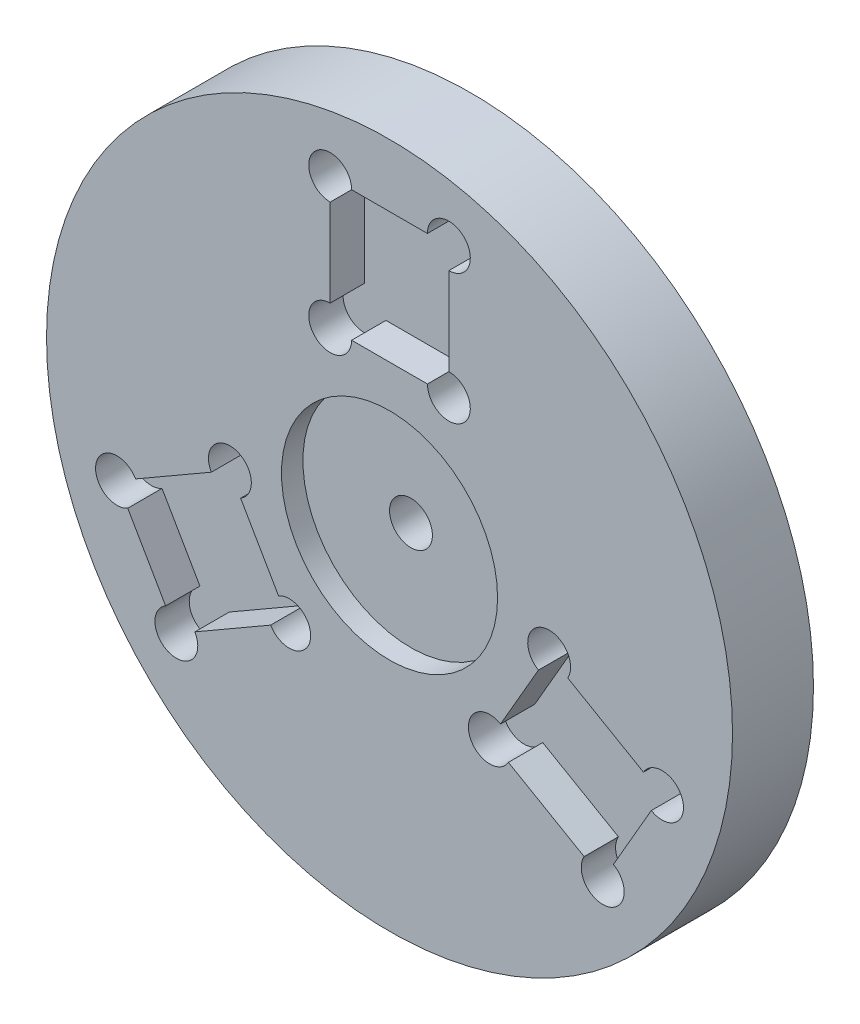
SolidWorks part; units mm, degrees
material "Beech"
ref_plane "Front Plane" through (0, 0, 0) normal (0, 0, 1) x (1, 0, 0)
ref_plane "Top Plane" through (0, 0, 0) normal (0, 1, 0) x (1, 0, 0)
ref_plane "Right Plane" through (0, 0, 0) normal (1, 0, 0) x (0, 0, -1)
sketch "Sketch1" plane through (0, 0, 0) normal (0, 0, 1) x (1, 0, 0)
  line L1 (-50.8, 50.8) -> (50.8, 50.8) construction
  line L2 (-50.8, 50.8) -> (-50.8, -50.8) construction
  line L3 (-50.8, -50.8) -> (50.8, -50.8) construction
  line L4 (50.8, 50.8) -> (50.8, -50.8) construction
  line L5 (-50.8, 50.8) -> (50.8, -50.8) construction
  line L6 (-50.8, -50.8) -> (50.8, 50.8) construction
  circle A0 centre (0, 0) radius 50.8
  point P0 (0, 0)
  dimension "D1" = 101.6
extrude "Boss-Extrude1" add sketch "Sketch1" along normal blind 11.9888
sketch "coupling circle" plane through (0, 0, 11.9888) normal (0, 0, 1) x (1, 0, 0)
  circle A0 centre (0, 0) radius 31.75
  dimension "D1" = 63.5
sketch "Sketch3" plane through (0, 0, 11.9888) normal (0, 0, 1) x (1, 0, 0)
  line L1 (-8.7871, 41.529) -> (8.7871, 41.529)
  line L2 (-8.7871, 41.529) -> (-8.7871, 22.225)
  line L3 (-8.7871, 22.225) -> (8.7871, 22.225)
  line L4 (8.7871, 41.529) -> (8.7871, 22.225)
  line L5 (-8.7871, 41.529) -> (8.7871, 22.225) construction
  line L6 (-8.7871, 22.225) -> (8.7871, 41.529) construction
  circle A1 centre (0, 0) radius 31.75 construction
  point P0 (0, 31.877)
  dimension "D1" = 17.5743
  dimension "D2" = 9.525
  dimension "D3" = 19.304
extrude "Cut-Extrude1" cut sketch "Sketch3" against normal blind 5.08
sketch "Sketch7" plane through (0, 0, 11.9888) normal (0, 0, 1) x (1, 0, 0)
  circle A0 centre (-8.7871, 41.529) radius 3.175
  circle A1 centre (-8.7871, 22.225) radius 3.175
  circle A2 centre (8.7871, 22.225) radius 3.175
  circle A3 centre (8.7871, 41.529) radius 3.175
  dimension "D1" = 6.35
extrude "corner reliefs" cut sketch "Sketch7" against normal up to surface (5.08 mm away) up to face at (0, 31.877, 6.9088)
ref_axis "Axis1" through (0, 0, 11.9888) along (0, 0, 1)
pattern_circular "CirPattern1" count 3 over 360 about axis through (0, 0, 11.9888) along (0, 0, 1) of "Cut-Extrude1", "corner reliefs"
sketch "Sketch5" plane through (0, 0, 11.9888) normal (0, 0, 1) x (1, 0, 0)
  circle A0 centre (0, 0) radius 16.002
  dimension "D1" = 32.004
extrude "magnet inset" cut sketch "Sketch5" against normal blind 3.175
sketch "Sketch6" plane through (0, 0, 8.8138) normal (0, 0, 1) x (1, 0, 0)
  circle A0 centre (0, 0) radius 3.175
  dimension "D1" = 6.35
extrude "central hole" cut sketch "Sketch6" against normal through all
equation "\"coupling_diam\"= 2.5"
equation "\"plate_diam\"= 4"
